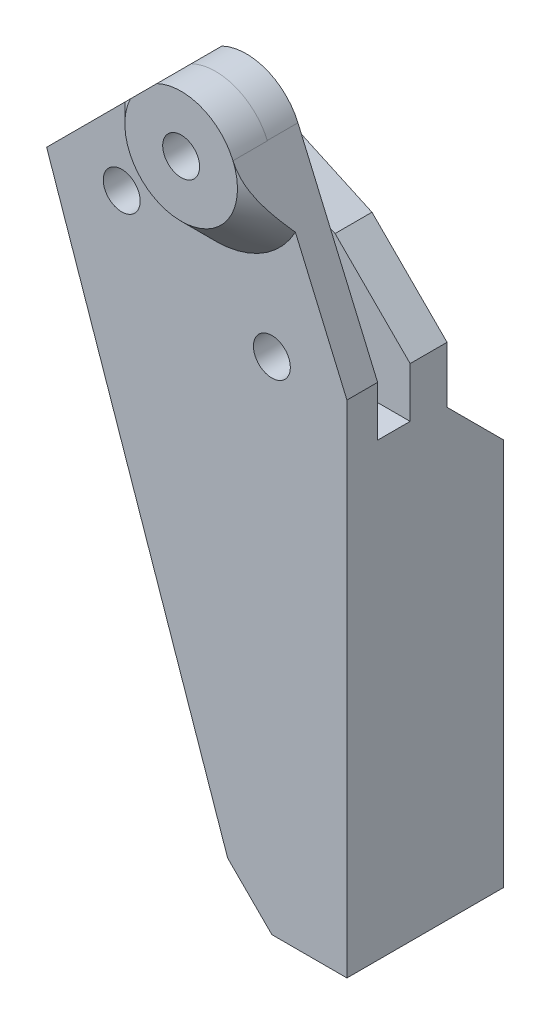
SolidWorks part; units mm, degrees
material "ABS"
ref_plane "Płaszczyzna przednia" through (0, 0, 0) normal (0, 0, 1) x (1, 0, 0)
ref_plane "Płaszczyzna górna" through (0, 0, 0) normal (0, 1, 0) x (1, 0, 0)
ref_plane "Płaszczyzna prawa" through (0, 0, 0) normal (1, 0, 0) x (0, 0, -1)
sketch "Szkic1" plane through (0, 0, 0) normal (0, 0, 1) x (1, 0, 0)
  line L0 (-24, 11) -> (-24, 23)
  line L1 (-24, 11) -> (-36, 11)
  line L2 (-24, 23) -> (-36, 11)
  line L3 (0, 0) -> (0, 12)
  line L4 (0, 12) -> (-24, 23)
  line L5 (0, 0) -> (12, 0)
  line L6 (0, 12) -> (12, 0)
  line L7 (0, 0) -> (0, -80)
  line L8 (0, -80) -> (12, -80)
  line L9 (0, -80) -> (-7.0711, -72.9289)
  line L10 (-7.0711, -72.9289) -> (-36, 11)
  line L11 (12, -80) -> (12, 0)
  circle A0 centre (0, 0) radius 2.95
  circle A1 centre (-24, 11) radius 2.95
  dimension "D1" = 5.9
  dimension "D2" = 24
  dimension "D3" = 5.9
  dimension "D4" = 11
  dimension "D5" = 12
  dimension "D6" = 12
  dimension "D7" = 12
  dimension "D8" = 12
  dimension "D9" = 80
  dimension "D10" = 12
  dimension "D11" = 135
  dimension "D12" = 10
extrude "Dodanie-wyciągnięcie1" add sketch "Szkic1" along normal blind 25 contours A1 L0 L2 L1 | A1 L1 L10 L9 L7 A0 L3 L4 L0 | A0 L5 L6 L3 | A0 L7 L8 L11 L5 region at (-28.2882, 15.2882, 0) region at (-12.4584, -19.8234, 0) region at (4.2882, 4.2882, 0) region at (6.034, -40.2779, 0)
sketch "Szkic3" plane through (12, 0, 0) normal (1, 0, 0) x (0, 0, -1)
  line L0 (-20.1, 17) -> (-20.1, -8)
  line L1 (-25, -80) -> (-25, 0) construction
  line L2 (-14.9, 17) -> (-14.9, -8)
  line L3 (-9, 17) -> (-9, -8)
  line L4 (-4, 17) -> (-4, -8)
  line L5 (0, -80) -> (0, 0) construction
  line L6 (-25, -8) -> (0, -8)
  line L7 (-25, 0) -> (0, 0) construction
  line L8 (-25, 17) -> (0, 17)
  line L9 (-25, 12) -> (-25, 0) construction
  line L10 (0, 12) -> (0, 0) construction
  line M8 (0, 0) -> (-25, 0)
  dimension "D1" = 4.9
  dimension "D2" = 10.1
  dimension "D3" = 4
  dimension "D4" = 9
  dimension "D5" = 8
  dimension "D6" = 25
extrude "Wytnij-wyciągnięcie1" cut sketch "Szkic3" against normal blind 20 contours L8 L0 L2 M8 | L0 L6 L2 M8 | L8 L3 L4 M8 | L3 L6 L4 M8 region at (12, 8.5, 17.5) region at (12, -4, 17.5) region at (12, 8.5, 6.5) region at (12, -4, 6.5)
sketch "Szkic4" plane through (12, 0, 0) normal (1, 0, 0) x (0, 0, -1)
  line L5 (-9, 12) -> (-9, 0) construction
  line L6 (-9, 4) -> (-4, 4)
  line L7 (-9, 4) -> (-9, 23)
  line L8 (-9, 23) -> (-4, 23)
  line L9 (-4, 4) -> (-4, 23)
  line L10 (-25, 23) -> (0, 23) construction
  dimension "D1" = 5
  dimension "D2" = 19
extrude "Wytnij-wyciągnięcie2" cut sketch "Szkic4" against normal blind 58
chamfer "Sfazowanie1" distance 6 angle 45 1 edges at (-8, -8, 17.5)
chamfer "Sfazowanie2" distance 12 angle 45 1 edges at (-8, 4, 6.5)
chamfer "Sfazowanie3" distance 2 angle 30 2 edges at (-8, 6.8333, 14.9) (-8, 6.8333, 20.1) first distance on face at (-8, 6.8333, 17.5)
sketch "Szkic5" plane through (0, 0, 25) normal (0, 0, 1) x (1, 0, 0)
  line L0 (-24, 23) -> (-12.8786, 34.1212)
  line L1 (-24, 23) -> (0, 12)
  line L4 (12, 0) -> (-0.7344, 29.5607)
  line L7 (12, 0) -> (0, 12)
  circle A0 centre (-9, 26) radius 2.95
  arc A5 (-0.7344, 29.5607) -> (-12.8786, 34.1212) centre (-9, 26) ccw
  line M11 (0, 12) -> (-24, 23)
  dimension "D3" = 5.9
  dimension "D1" = 26
  dimension "D2" = 9
extrude "Dodanie-wyciągnięcie2" add sketch "Szkic5" against normal blind 4.9 contours A0 M11 | A0 M11 region at (-6.0366, 21.6949, 25)
sketch "Szkic6" plane through (12, 0, 0) normal (1, 0, 0) x (0, 0, -1)
  line L1 (-9, -8) -> (0, -8)
  line L2 (-9, -8) -> (-9, 23)
  line L3 (-9, 23) -> (0, 23)
  line L4 (0, -8) -> (0, 23)
extrude "Wytnij-wyciągnięcie3" cut sketch "Szkic6" against normal blind 60
chamfer "Sfazowanie4" distance 10 angle 45 1 edges at (-8.7255, -8, 0)
sketch "Szkic8" plane through (0, 0, 25) normal (0, 0, 1) x (1, 0, 0)
  line L0 (-17.1214, 29.8785) -> (-12.8784, 34.1214)
  circle A0 centre (-9, 26) radius 2.95
  arc A1 (-17.1214, 29.8785) -> (-12.8784, 34.1214) centre (-9, 26) ccw
  dimension "D1" = 18
  dimension "D2" = 5.9
extrude "Dodanie-wyciągnięcie3" add sketch "Szkic8" along normal blind 5.5
chamfer "Sfazowanie5" distance 5.5 angle 45 1 edges at (-9.196, 17.0021, 25)
sketch "Szkic10" plane through (12, 0, 0) normal (1, 0, 0) x (0, 0, -1)
  line L0 (-20, -23) -> (-20, -75)
  line L1 (-20, -75) -> (-5, -75)
  line L2 (-5, -75) -> (-5, -23)
  line L3 (-5, -23) -> (-20, -23)
  line L4 (-25, -80) -> (0, -80) construction
  line L5 (0, -80) -> (0, -18) construction
  line L6 (-25, -80) -> (-25, 0) construction
  dimension "D1" = 5
  dimension "D2" = 5
  dimension "D3" = 5
  dimension "D4" = 5
extrude "Wytnij-wyciągnięcie6" cut sketch "Szkic10" against normal blind 70 from offset 5 offset against normal yes
chamfer "Sfazowanie9" distance 7 angle 60 4 edges at (7, -49, 20) (7, -75, 12.5) (7, -49, 5) (7, -23, 12.5) first distance on face at (7, -49, 12.5)
chamfer "Sfazowanie10" distance 3 angle 45 1 edges at (-15.4226, 19.0687, 20.1)
